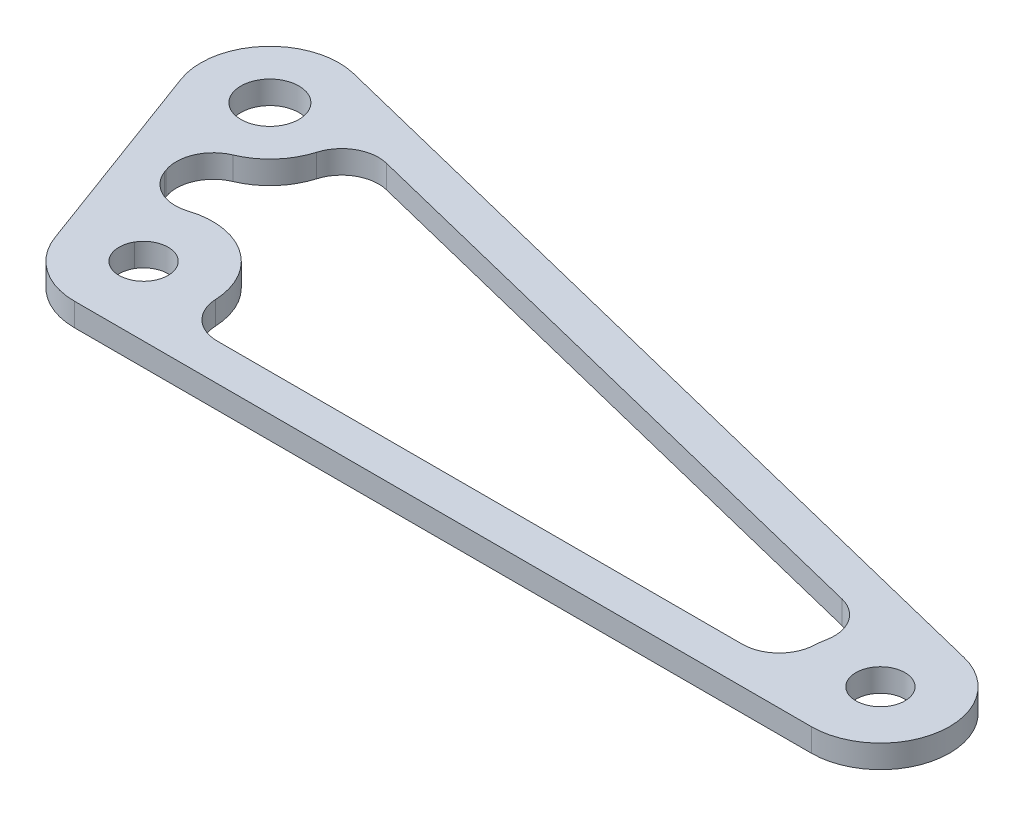
SolidWorks part; units mm, degrees
material "6061-T6 (SS)"
ref_plane "Front Plane" through (0, 0, 0) normal (0, 0, 1) x (1, 0, 0)
ref_plane "Top Plane" through (0, 0, 0) normal (0, 1, 0) x (1, 0, 0)
ref_plane "Right Plane" through (0, 0, 0) normal (1, 0, 0) x (0, 0, -1)
sketch "Sketch1" plane through (0, 0, 0) normal (0, 1, 0) x (1, 0, 0)
  line L0 (0, 0) -> (101.5644, 0) construction
  line L1 (101.5644, 0) -> (-10.2264, 27.6351) construction
  line L2 (-10.2264, 27.6351) -> (0, 0) construction
  line L3 (-23.321, 35.5752) -> (-7.3987, -7.4519)
  line L4 (-4.421, -9.525) -> (153.7124, -9.525)
  line L5 (154.4744, -3.2678) -> (-19.5814, 39.7594)
  circle A0 centre (0, 0) radius 3.3782
  circle A1 centre (-10.2264, 27.6351) radius 4
  circle A2 centre (101.5644, 0) radius 3.3782
  arc A6 (154.4744, -3.2678) -> (153.7124, -9.525) centre (153.7124, -6.35) cw
  arc A7 (-4.421, -9.525) -> (-7.3987, -7.4519) centre (-4.421, -6.35) cw
  arc A8 (-19.5814, 39.7594) -> (-23.321, 35.5752) centre (-20.3433, 36.6771) ccw
  circle A9 centre (101.5644, 0) radius 9.525
  circle A10 centre (0, 0) radius 9.525
  circle A11 centre (-10.2264, 27.6351) radius 9.525
  dimension "D4" = 6.7564
  dimension "D5" = 8
  dimension "D6" = 9.525
  dimension "D2" = 29.4665
  dimension "D3" = 115.156
  dimension "D7" = 9.525
  dimension "D8" = 9.525
  dimension "D13" = 101.5644
extrude "Boss-Extrude2" add sketch "Sketch1" along normal blind 3.175 contours A11 L3 A10 L4 A9 L5 | A10 A0 | A9 A2 | A11 A1 region at (39.9055, 0, -8.433) region at (-17.1274, 0, -33.8029) region at (-1.6316, 0, -9.1106) region at (108.8522, 0, -5.7056)
sketch "Sketch2" plane through (0, 3.175, 0) normal (0, 1, 0) x (1, 0, 0)
  line L0 (-10.2264, 27.6351) -> (101.5644, 0)
  line L1 (101.5644, 0) -> (0, 0)
  line L2 (0, 0) -> (-10.2264, 27.6351)
  line L3 (8.4242, -4.445) -> (93.1402, -4.445)
  line L4 (-0.9817, 29.9285) -> (94.4531, 6.3367)
  line L5 (-17.3188, 33.993) -> (-1.2451, -9.4433)
  line L6 (-19.1594, 24.3294) -> (-8.933, -3.3057) construction
  line L7 (103.8502, 9.2467) -> (-7.9406, 36.8817) construction
  line L8 (0, -9.525) -> (101.5644, -9.525) construction
  circle A0 centre (-10.2264, 27.6351) radius 9.525
  circle A1 centre (0, 0) radius 9.525
  circle A2 centre (101.5644, 0) radius 9.525
  circle A4 centre (101.5644, 0) radius 3.3782 construction
  arc A5 (101.5644, -9.525) -> (103.8502, 9.2467) centre (101.5644, 0) ccw construction
  arc A6 (-7.9406, 36.8817) -> (-19.1594, 24.3294) centre (-10.2264, 27.6351) ccw construction
  arc A7 (-8.933, -3.3057) -> (0, -9.525) centre (0, 0) ccw construction
  point P25 (0, 0)
  point P26 (0, 0)
  point P27 (0, 0)
  point P28 (0, 0)
  dimension "D1" = 5.08
  dimension "D2" = 5.08
  dimension "D3" = 5.08
extrude "Cut-Extrude1" cut sketch "Sketch2" against normal through all contours A2 L0 A0 L2 A1 L1 | A1 L2 A0 L5 | A2 L4 A0 L0 | A2 L1 A1 L3 region at (46.2043, 3.175, -15.9832) region at (33.0412, 3.175, -9.1125) region at (-7.2654, 3.175, -13.0211) region at (50.7822, 3.175, 2.2322)
fillet "Fillet1" radius 5.08 6 edges at (94.4531, 1.5875, -6.3367) (93.1402, 1.5875, 4.445) (8.4242, 1.5875, 4.445) (-0.9817, 1.5875, -29.9285) (-11.4715, 1.5875, -18.1918) (-7.0924, 1.5875, -6.358)
ref_axis "Axis1" through (0, 3.175, 0) along (0, -1, 0)
ref_plane "Plane1" through (0, 0, 0) normal (0.4967, 0, -0.8679) x (0, -1, 0)
split line "Split Line1"
ref_point "Point2"
